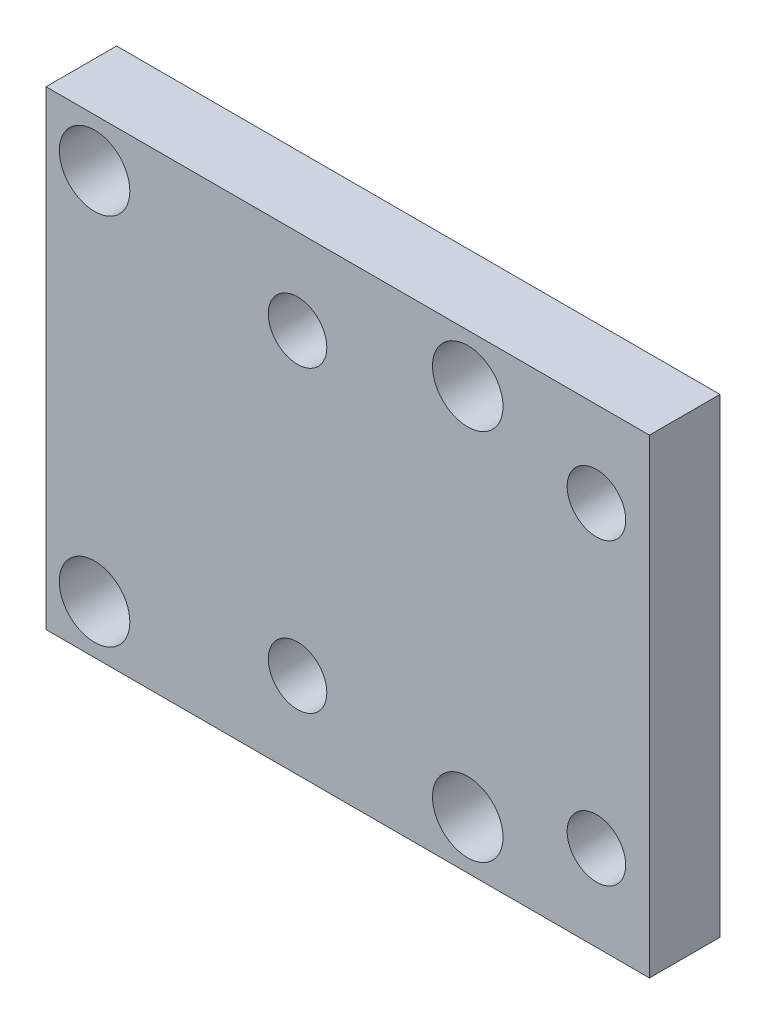
SolidWorks part; units mm, degrees
ref_plane "Front Plane" through (0, 0, 0) normal (0, 0, 1) x (1, 0, 0)
ref_plane "Top Plane" through (0, 0, 0) normal (0, 1, 0) x (1, 0, 0)
ref_plane "Right Plane" through (0, 0, 0) normal (1, 0, 0) x (0, 0, -1)
sketch "Sketch1" plane through (0, 0, 0) normal (0, 0, 1) x (1, 0, 0)
  line L1 (-14.09, 0) -> (-65.43, 0)
  line L2 (-14.09, 0) -> (-14.09, -40)
  line L3 (-14.09, -40) -> (-65.43, -40)
  line L4 (-65.43, 0) -> (-65.43, -40)
  dimension "D1" = 51.34
  dimension "D2" = 40
extrude "Boss-Extrude1" add sketch "Sketch1" along normal blind 6
sketch "Sketch2" plane through (0, 0, 0) normal (0, 0, 1) x (1, 0, 0)
  line L4 (-65.43, 0) -> (-65.43, -40) construction
  line L6 (-65.43, -40) -> (-14.09, -40) construction
  circle A6 centre (-61.3, -35.875) radius 2
  circle A7 centre (-29.55, -35.875) radius 2
  circle A8 centre (-29.55, -4.125) radius 2
  circle A9 centre (-61.3, -4.125) radius 2
  dimension "D1" = 31.75
  dimension "D2" = 31.75
  dimension "D3" = 4.13
  dimension "D4" = 4
  dimension "D5" = 4.125
  dimension "D6" = 2
  dimension "D7" = 2
extrude "Cut-Extrude2" cut sketch "Sketch2" along normal through all
sketch "Sketch8" plane through (0, 0, 6) normal (0, 0, 1) x (1, 0, 0)
  circle A0 centre (-61.3, -4.125) radius 3
  circle A3 centre (-29.55, -4.125) radius 3
  circle A4 centre (-29.55, -35.875) radius 3
  circle A5 centre (-61.3, -35.875) radius 3
  dimension "D1" = 6
  dimension "D2" = 2
  dimension "D3" = 2
extrude "Cut-Extrude6" cut sketch "Sketch8" against normal blind 5
sketch "Sketch9" plane through (0, 0, 6) normal (0, 0, 1) x (1, 0, 0)
  line L0 (-18.6008, -7.27) -> (-18.6008, -43.6541) construction
  line L1 (-18.6008, -7.27) -> (-44.0308, -7.27) construction
  line L2 (-44.0308, -7.27) -> (-44.0308, -32.7) construction
  line L3 (-44.0308, -32.7) -> (-18.6008, -32.7) construction
  circle A0 centre (-44.0308, -7.27) radius 2.49
  circle A1 centre (-18.6008, -7.27) radius 2.49
  circle A2 centre (-44.0308, -32.7) radius 2.49
  circle A3 centre (-18.6008, -32.7) radius 2.49
  dimension "D2" = 25.43
  dimension "D3" = 25.43
  dimension "D4" = 2
  dimension "D5" = 2
extrude "Cut-Extrude7" cut sketch "Sketch9" against normal up to surface (6 mm away) up to face at (-27.55, -4.125, 0)
equation "\"hole_screw_1_4_20\"= 6"
equation "\"inch\"=25.43"
